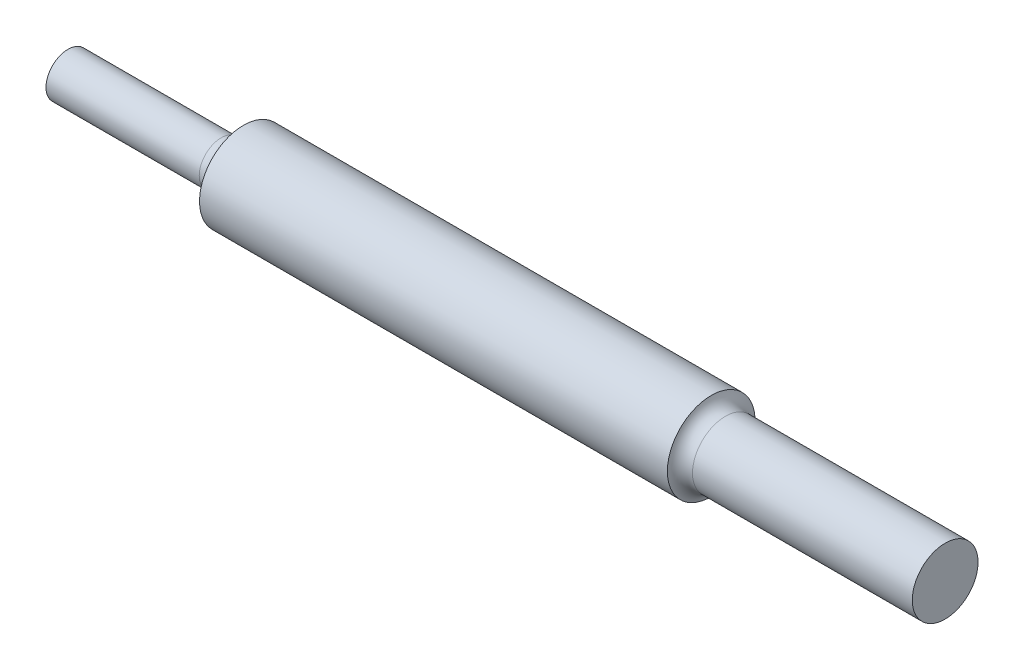
SolidWorks part; units mm, degrees
ref_plane "Front Plane" through (0, 0, 0) normal (0, 0, 1) x (1, 0, 0)
ref_plane "Top Plane" through (0, 0, 0) normal (0, 1, 0) x (1, 0, 0)
ref_plane "Right Plane" through (0, 0, 0) normal (1, 0, 0) x (0, 0, -1)
sketch "Sketch1" plane through (0, 0, 0) normal (0, 0, 1) x (1, 0, 0)
  line L0 (-816.8743, 0) -> (1156.8037, 0) construction
  line L23 (-101.6, 19.05) -> (101.6, 19.05)
  line L27 (-101.6, -19.05) -> (101.6, 19.05) construction
  line L28 (-101.6, 19.05) -> (101.6, -19.05) construction
  line L31 (-101.6, 9.525) -> (-177.8, 9.525)
  line L32 (-177.8, 0) -> (-177.8, 9.525)
  line L35 (101.6, 14.2875) -> (203.2, 14.2875)
  line L36 (203.2, 0) -> (203.2, 14.2875)
  line L37 (-101.6, 9.525) -> (-101.6, 19.05)
  line L38 (101.6, 14.2875) -> (101.6, 19.05)
  line L39 (-177.8, 0) -> (203.2, 0)
  point P0 (0, 0)
  dimension "D1" = 19.05
  dimension "D2" = 38.1
  dimension "D3" = 28.575
  dimension "D4" = 76.2
  dimension "D5" = 203.2
  dimension "D6" = 101.6
revolve "Revolve3" add sketch "Sketch1" angle 360 about L39
fillet "Fillet1" radius 9.652 1 edges at (-101.6, 0, 9.525)
fillet "Fillet2" radius 6.35 1 edges at (101.6, 0, 14.2875)
